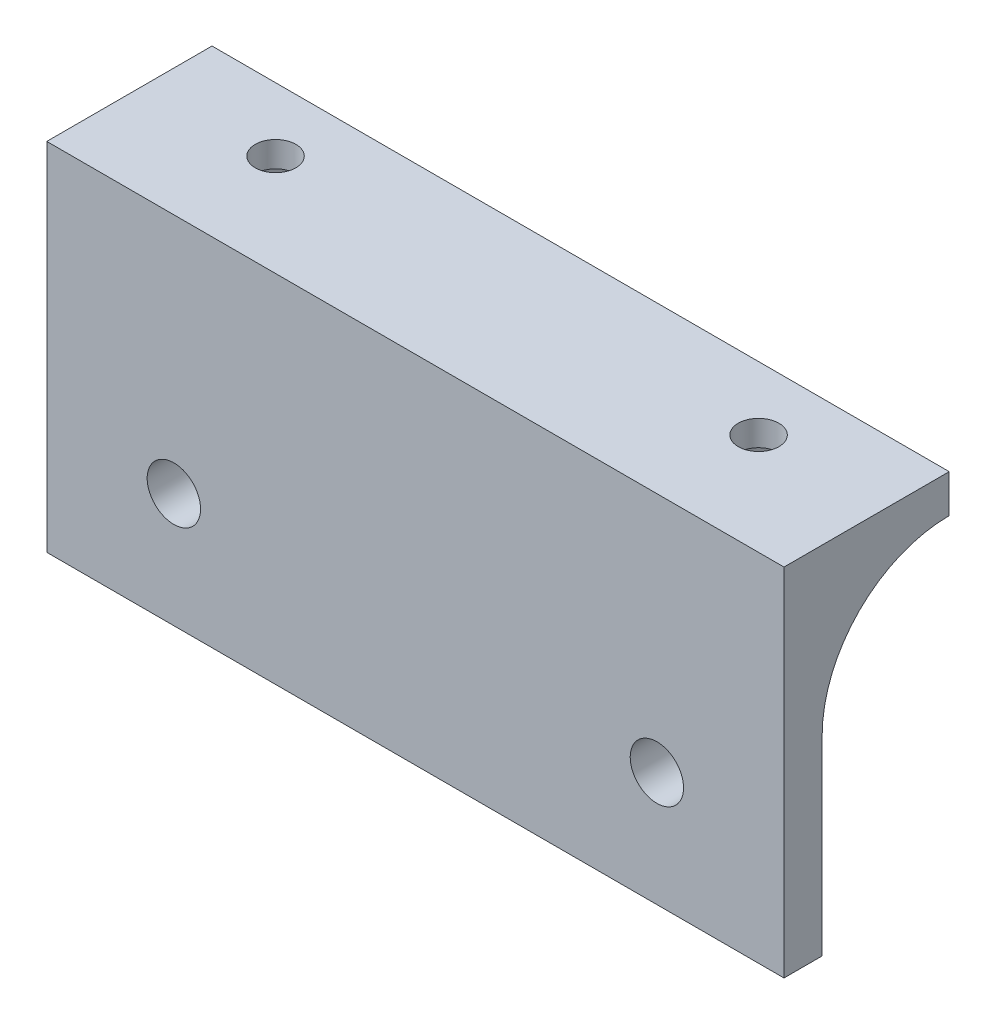
SolidWorks part; units mm, degrees
ref_plane "Front Plane" through (0, 0, 0) normal (0, 0, 1) x (1, 0, 0)
ref_plane "Top Plane" through (0, 0, 0) normal (0, 1, 0) x (1, 0, 0)
ref_plane "Right Plane" through (0, 0, 0) normal (1, 0, 0) x (0, 0, -1)
sketch "Rigidbot" plane through (0, 0, 0) normal (0, 0, 1) x (1, 0, 0)
  line L0 (-29, -5) -> (29, -5) construction
  line L1 (-29, 14) -> (29, 14)
  line L2 (-29, 14) -> (-29, -14)
  line L3 (-29, -14) -> (29, -14)
  line L4 (29, 14) -> (29, -14)
  line L5 (-29, 14) -> (29, -14) construction
  line L6 (-29, -14) -> (29, 14) construction
  line L7 (0, 14) -> (0, -14) construction
  circle A0 centre (-19, -5) radius 2.1
  circle A1 centre (19, -5) radius 2.1
  point P0 (0, 0)
  dimension "D3" = 4.2
  dimension "D1" = 58
  dimension "D2" = 38
  dimension "D4" = 9
  dimension "D5" = 28
extrude "Boss-Rigidbot" add sketch "Rigidbot" along normal blind 3
sketch "Case" plane through (0, 14, 0) normal (0, 1, 0) x (1, 0, 0)
  line L0 (-29, -3) -> (29, -3)
  line L1 (29, -3) -> (29, 10)
  line L2 (29, 10) -> (-29, 10)
  line L3 (-29, 10) -> (-29, -3)
  line L4 (-29, 5) -> (29, 5) construction
  line L5 (0, 10) -> (0, -3) construction
  circle A0 centre (-19, 5) radius 1.6
  circle A1 centre (19, 5) radius 1.6
  dimension "D1" = 3.2
  dimension "D2" = 38
  dimension "D3" = 5
  dimension "D4" = 8
extrude "Boss-Case" add sketch "Case" against normal blind 3
sketch "M3Nut" plane through (0, 14, 0) normal (0, 1, 0) x (1, 0, 0)
  line L0 (0, 10) -> (0, -3) construction
  line L1 (-15.9978, 5) -> (-17.4989, 7.6)
  line L2 (-17.4989, 7.6) -> (-20.5011, 7.6)
  line L3 (-20.5011, 7.6) -> (-22.0022, 5)
  line L4 (-22.0022, 5) -> (-20.5011, 2.4)
  line L5 (-20.5011, 2.4) -> (-17.4989, 2.4)
  line L6 (-17.4989, 2.4) -> (-15.9978, 5)
  line L7 (29, 10) -> (-29, 10) construction
  line L8 (29, -3) -> (-29, -3) construction
  line L9 (17.4989, 2.4) -> (15.9978, 5)
  line L10 (20.5011, 2.4) -> (17.4989, 2.4)
  line L11 (22.0022, 5) -> (20.5011, 2.4)
  line L12 (20.5011, 7.6) -> (22.0022, 5)
  line L13 (17.4989, 7.6) -> (20.5011, 7.6)
  line L14 (15.9978, 5) -> (17.4989, 7.6)
  circle A0 centre (-19, 5) radius 2.6 construction
  circle A1 centre (19, 5) radius 2.6 construction
  dimension "D1" = 5.2
extrude "Cut-M3Nut" cut sketch "M3Nut" against normal blind 10 from offset 2 offset against normal yes
fillet "Fillet" radius 10 1 edges at (0, 11, 0)
